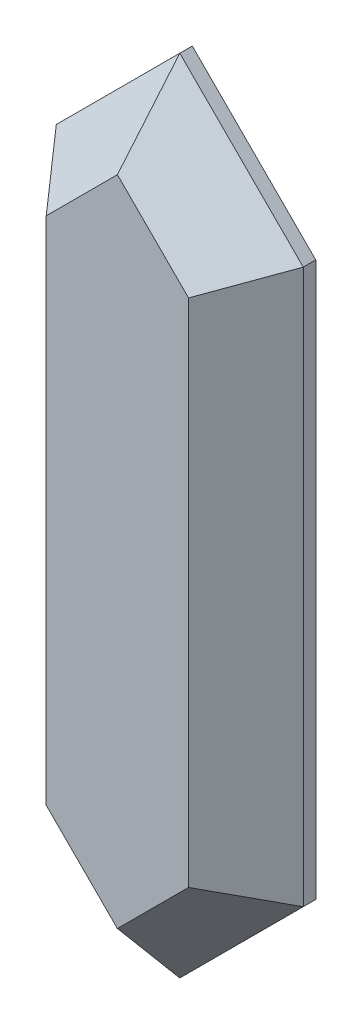
SolidWorks part; units mm, degrees
ref_plane "Спереди" through (0, 0, 0) normal (0, 0, 1) x (1, 0, 0)
ref_plane "Сверху" through (0, 0, 0) normal (0, 1, 0) x (1, 0, 0)
ref_plane "Справа" through (0, 0, 0) normal (1, 0, 0) x (0, 0, -1)
sketch "Skizze1" plane through (0, 0, 0) normal (0, 0, 1) x (1, 0, 0)
  line L0 (-19.799, 44.3) -> (0, 64.099)
  line L1 (0, 64.099) -> (19.799, 44.3)
  line L2 (19.799, 44.3) -> (19.799, -44.5)
  line L3 (19.799, -44.5) -> (0, -64.299)
  line L4 (0, -64.299) -> (-19.799, -44.5)
  line L5 (-19.799, -44.5) -> (-19.799, 44.3)
  line L6 (0, -64.299) -> (0, 76.8777) construction
  line L7 (-19.799, -44.5) -> (59.397, -44.5) construction
  dimension "D1" = 90
  dimension "D2" = 88.8
  dimension "D3" = 28
  dimension "D4" = 90
  dimension "D5" = 44.5
extrude "Бобышка-Вытянуть1" add sketch "Skizze1" along normal blind 2
sketch "Эскиз1" plane through (0, 0, 2) normal (0, 0, 1) x (1, 0, 0)
  line L6 (-19.799, 44.3) -> (-19.799, -44.5)
  line L7 (-19.799, -44.5) -> (0, -64.299)
  line L8 (0, -64.299) -> (19.799, -44.5)
  line L9 (19.799, -44.5) -> (19.799, 44.3)
  line L10 (19.799, 44.3) -> (0, 64.099)
  line L11 (0, 64.099) -> (-19.799, 44.3)
  line L12 (-19.799, 44.3) -> (-19.799, -44.5)
  line L13 (-19.799, -44.5) -> (0, -64.299)
  line L14 (0, -64.299) -> (19.799, -44.5)
  line L15 (19.799, -44.5) -> (19.799, 44.3)
  line L16 (19.799, 44.3) -> (0, 64.099)
  line L17 (0, 64.099) -> (-19.799, 44.3)
  dimension "D1" = 0
extrude "Бобышка-Вытянуть2" add sketch "Эскиз1" along normal blind 10 draft 40
sketch "Эскиз2" plane through (0, 0, 0) normal (0, 0, -1) x (-1, 0, 0)
  line L0 (-17.999, 43.5544) -> (0, 61.5534)
  line L1 (0, 61.5534) -> (17.999, 43.5544)
  line L2 (17.999, 43.5544) -> (17.999, -43.7544)
  line L3 (17.999, -43.7544) -> (0, -61.7534)
  line L4 (0, -61.7534) -> (-17.999, -43.7544)
  line L5 (-17.999, -43.7544) -> (-17.999, 43.5544)
  line L6 (-19.799, 44.3) -> (0, 64.099) construction
  line L7 (0, 64.099) -> (19.799, 44.3) construction
  line L8 (-19.799, -44.5) -> (-19.799, 44.3) construction
  line L9 (0, -64.299) -> (-19.799, -44.5) construction
  line L10 (19.799, -44.5) -> (0, -64.299) construction
  line L11 (19.799, 44.3) -> (19.799, -44.5) construction
  dimension "D1" = 1.8
  dimension "D2" = 1.8
  dimension "D3" = 1.8
  dimension "D4" = 1.8
  dimension "D5" = 1.8
  dimension "D6" = 1.8
extrude "Вырез-Вытянуть1" cut sketch "Эскиз2" against normal blind 2
sketch "Эскиз3" plane through (0, 0, 2) normal (0, 0, -1) x (-1, 0, 0)
  line L6 (-17.999, 43.5544) -> (-17.999, -43.7544)
  line L7 (-17.999, -43.7544) -> (0, -61.7534)
  line L8 (0, -61.7534) -> (17.999, -43.7544)
  line L9 (17.999, -43.7544) -> (17.999, 43.5544)
  line L10 (17.999, 43.5544) -> (0, 61.5534)
  line L11 (0, 61.5534) -> (-17.999, 43.5544)
  line L12 (-17.999, 43.5544) -> (-17.999, -43.7544)
  line L13 (-17.999, -43.7544) -> (0, -61.7534)
  line L14 (0, -61.7534) -> (17.999, -43.7544)
  line L15 (17.999, -43.7544) -> (17.999, 43.5544)
  line L16 (17.999, 43.5544) -> (0, 61.5534)
  line L17 (0, 61.5534) -> (-17.999, 43.5544)
  dimension "D1" = 0
extrude "Вырез-Вытянуть2" cut sketch "Эскиз3" against normal blind 7 draft 40
sketch "Эскиз4" plane through (0, 0, 9) normal (0, 0, -1) x (-1, 0, 0)
  line L12 (-0.6625, 48.8702) -> (-1.7495, 49.4689)
  line L13 (-1.7495, 49.4689) -> (-2.8115, 48.827)
  line L14 (-2.8115, 48.827) -> (-2.7865, 47.5863)
  line L15 (-2.7865, 47.5863) -> (-1.6996, 46.9876)
  line L16 (-1.6996, 46.9876) -> (-0.6376, 47.6295)
  line L17 (-0.6376, 47.6295) -> (-0.6625, 48.8702)
  line L18 (2.7875, 48.8702) -> (1.7005, 49.4689)
  line L19 (1.7005, 49.4689) -> (0.6385, 48.827)
  line L20 (0.6385, 48.827) -> (0.6635, 47.5863)
  line L21 (0.6635, 47.5863) -> (1.7504, 46.9876)
  line L22 (1.7504, 46.9876) -> (2.8124, 47.6295)
  line L23 (2.8124, 47.6295) -> (2.7875, 48.8702)
  line L36 (-4.1125, 44.8702) -> (-5.1995, 45.4689)
  line L37 (-5.1995, 45.4689) -> (-6.2615, 44.827)
  line L38 (-6.2615, 44.827) -> (-6.2365, 43.5863)
  line L39 (-6.2365, 43.5863) -> (-5.1496, 42.9876)
  line L40 (-5.1496, 42.9876) -> (-4.0876, 43.6295)
  line L41 (-4.0876, 43.6295) -> (-4.1125, 44.8702)
  line L42 (-0.6625, 44.8702) -> (-1.7495, 45.4689)
  line L43 (-1.7495, 45.4689) -> (-2.8115, 44.827)
  line L44 (-2.8115, 44.827) -> (-2.7865, 43.5863)
  line L45 (-2.7865, 43.5863) -> (-1.6996, 42.9876)
  line L46 (-1.6996, 42.9876) -> (-0.6376, 43.6295)
  line L47 (-0.6376, 43.6295) -> (-0.6625, 44.8702)
  line L48 (2.7875, 44.8702) -> (1.7005, 45.4689)
  line L49 (1.7005, 45.4689) -> (0.6385, 44.827)
  line L50 (0.6385, 44.827) -> (0.6635, 43.5863)
  line L51 (0.6635, 43.5863) -> (1.7504, 42.9876)
  line L52 (1.7504, 42.9876) -> (2.8124, 43.6295)
  line L53 (2.8124, 43.6295) -> (2.7875, 44.8702)
  line L54 (6.2375, 44.8702) -> (5.1505, 45.4689)
  line L55 (5.1505, 45.4689) -> (4.0885, 44.827)
  line L56 (4.0885, 44.827) -> (4.1135, 43.5863)
  line L57 (4.1135, 43.5863) -> (5.2004, 42.9876)
  line L58 (5.2004, 42.9876) -> (6.2624, 43.6295)
  line L59 (6.2624, 43.6295) -> (6.2375, 44.8702)
  line L66 (-4.1125, 40.8702) -> (-5.1995, 41.4689)
  line L67 (-5.1995, 41.4689) -> (-6.2615, 40.827)
  line L68 (-6.2615, 40.827) -> (-6.2365, 39.5863)
  line L69 (-6.2365, 39.5863) -> (-5.1496, 38.9876)
  line L70 (-5.1496, 38.9876) -> (-4.0876, 39.6295)
  line L71 (-4.0876, 39.6295) -> (-4.1125, 40.8702)
  line L72 (-0.6625, 40.8702) -> (-1.7495, 41.4689)
  line L73 (-1.7495, 41.4689) -> (-2.8115, 40.827)
  line L74 (-2.8115, 40.827) -> (-2.7865, 39.5863)
  line L75 (-2.7865, 39.5863) -> (-1.6996, 38.9876)
  line L76 (-1.6996, 38.9876) -> (-0.6376, 39.6295)
  line L77 (-0.6376, 39.6295) -> (-0.6625, 40.8702)
  line L78 (2.7875, 40.8702) -> (1.7005, 41.4689)
  line L79 (1.7005, 41.4689) -> (0.6385, 40.827)
  line L80 (0.6385, 40.827) -> (0.6635, 39.5863)
  line L81 (0.6635, 39.5863) -> (1.7504, 38.9876)
  line L82 (1.7504, 38.9876) -> (2.8124, 39.6295)
  line L83 (2.8124, 39.6295) -> (2.7875, 40.8702)
  line L84 (6.2375, 40.8702) -> (5.1505, 41.4689)
  line L85 (5.1505, 41.4689) -> (4.0885, 40.827)
  line L86 (4.0885, 40.827) -> (4.1135, 39.5863)
  line L87 (4.1135, 39.5863) -> (5.2004, 38.9876)
  line L88 (5.2004, 38.9876) -> (6.2624, 39.6295)
  line L89 (6.2624, 39.6295) -> (6.2375, 40.8702)
  line L90 (9.6875, 40.8702) -> (8.6005, 41.4689)
  line L91 (8.6005, 41.4689) -> (7.5385, 40.827)
  line L92 (7.5385, 40.827) -> (7.5635, 39.5863)
  line L93 (7.5635, 39.5863) -> (8.6504, 38.9876)
  line L94 (8.6504, 38.9876) -> (9.7124, 39.6295)
  line L95 (9.7124, 39.6295) -> (9.6875, 40.8702)
  line L96 (-4.1125, 36.8702) -> (-5.1995, 37.4689)
  line L97 (-5.1995, 37.4689) -> (-6.2615, 36.827)
  line L98 (-6.2615, 36.827) -> (-6.2365, 35.5863)
  line L99 (-6.2365, 35.5863) -> (-5.1496, 34.9876)
  line L100 (-5.1496, 34.9876) -> (-4.0876, 35.6295)
  line L101 (-4.0876, 35.6295) -> (-4.1125, 36.8702)
  line L102 (-0.6625, 36.8702) -> (-1.7495, 37.4689)
  line L103 (-1.7495, 37.4689) -> (-2.8115, 36.827)
  line L104 (-2.8115, 36.827) -> (-2.7865, 35.5863)
  line L105 (-2.7865, 35.5863) -> (-1.6996, 34.9876)
  line L106 (-1.6996, 34.9876) -> (-0.6376, 35.6295)
  line L107 (-0.6376, 35.6295) -> (-0.6625, 36.8702)
  line L108 (2.7875, 36.8702) -> (1.7005, 37.4689)
  line L109 (1.7005, 37.4689) -> (0.6385, 36.827)
  line L110 (0.6385, 36.827) -> (0.6635, 35.5863)
  line L111 (0.6635, 35.5863) -> (1.7504, 34.9876)
  line L112 (1.7504, 34.9876) -> (2.8124, 35.6295)
  line L113 (2.8124, 35.6295) -> (2.7875, 36.8702)
  line L114 (6.2375, 36.8702) -> (5.1505, 37.4689)
  line L115 (5.1505, 37.4689) -> (4.0885, 36.827)
  line L116 (4.0885, 36.827) -> (4.1135, 35.5863)
  line L117 (4.1135, 35.5863) -> (5.2004, 34.9876)
  line L118 (5.2004, 34.9876) -> (6.2624, 35.6295)
  line L119 (6.2624, 35.6295) -> (6.2375, 36.8702)
  line L120 (9.6875, 36.8702) -> (8.6005, 37.4689)
  line L121 (8.6005, 37.4689) -> (7.5385, 36.827)
  line L122 (7.5385, 36.827) -> (7.5635, 35.5863)
  line L123 (7.5635, 35.5863) -> (8.6504, 34.9876)
  line L124 (8.6504, 34.9876) -> (9.7124, 35.6295)
  line L125 (9.7124, 35.6295) -> (9.6875, 36.8702)
  line L126 (-4.1125, 32.8702) -> (-5.1995, 33.4689)
  line L127 (-5.1995, 33.4689) -> (-6.2615, 32.827)
  line L128 (-6.2615, 32.827) -> (-6.2365, 31.5863)
  line L129 (-6.2365, 31.5863) -> (-5.1496, 30.9876)
  line L130 (-5.1496, 30.9876) -> (-4.0876, 31.6295)
  line L131 (-4.0876, 31.6295) -> (-4.1125, 32.8702)
  line L132 (-0.6625, 32.8702) -> (-1.7495, 33.4689)
  line L133 (-1.7495, 33.4689) -> (-2.8115, 32.827)
  line L134 (-2.8115, 32.827) -> (-2.7865, 31.5863)
  line L135 (-2.7865, 31.5863) -> (-1.6996, 30.9876)
  line L136 (-1.6996, 30.9876) -> (-0.6376, 31.6295)
  line L137 (-0.6376, 31.6295) -> (-0.6625, 32.8702)
  line L138 (2.7875, 32.8702) -> (1.7005, 33.4689)
  line L139 (1.7005, 33.4689) -> (0.6385, 32.827)
  line L140 (0.6385, 32.827) -> (0.6635, 31.5863)
  line L141 (0.6635, 31.5863) -> (1.7504, 30.9876)
  line L142 (1.7504, 30.9876) -> (2.8124, 31.6295)
  line L143 (2.8124, 31.6295) -> (2.7875, 32.8702)
  line L144 (6.2375, 32.8702) -> (5.1505, 33.4689)
  line L145 (5.1505, 33.4689) -> (4.0885, 32.827)
  line L146 (4.0885, 32.827) -> (4.1135, 31.5863)
  line L147 (4.1135, 31.5863) -> (5.2004, 30.9876)
  line L148 (5.2004, 30.9876) -> (6.2624, 31.6295)
  line L149 (6.2624, 31.6295) -> (6.2375, 32.8702)
  line L150 (9.6875, 32.8702) -> (8.6005, 33.4689)
  line L151 (8.6005, 33.4689) -> (7.5385, 32.827)
  line L152 (7.5385, 32.827) -> (7.5635, 31.5863)
  line L153 (7.5635, 31.5863) -> (8.6504, 30.9876)
  line L154 (8.6504, 30.9876) -> (9.7124, 31.6295)
  line L155 (9.7124, 31.6295) -> (9.6875, 32.8702)
  line L156 (-4.1125, 28.8702) -> (-5.1995, 29.4689)
  line L157 (-5.1995, 29.4689) -> (-6.2615, 28.827)
  line L158 (-6.2615, 28.827) -> (-6.2365, 27.5863)
  line L159 (-6.2365, 27.5863) -> (-5.1496, 26.9876)
  line L160 (-5.1496, 26.9876) -> (-4.0876, 27.6295)
  line L161 (-4.0876, 27.6295) -> (-4.1125, 28.8702)
  line L162 (-0.6625, 28.8702) -> (-1.7495, 29.4689)
  line L163 (-1.7495, 29.4689) -> (-2.8115, 28.827)
  line L164 (-2.8115, 28.827) -> (-2.7865, 27.5863)
  line L165 (-2.7865, 27.5863) -> (-1.6996, 26.9876)
  line L166 (-1.6996, 26.9876) -> (-0.6376, 27.6295)
  line L167 (-0.6376, 27.6295) -> (-0.6625, 28.8702)
  line L168 (2.7875, 28.8702) -> (1.7005, 29.4689)
  line L169 (1.7005, 29.4689) -> (0.6385, 28.827)
  line L170 (0.6385, 28.827) -> (0.6635, 27.5863)
  line L171 (0.6635, 27.5863) -> (1.7504, 26.9876)
  line L172 (1.7504, 26.9876) -> (2.8124, 27.6295)
  line L173 (2.8124, 27.6295) -> (2.7875, 28.8702)
  line L174 (6.2375, 28.8702) -> (5.1505, 29.4689)
  line L175 (5.1505, 29.4689) -> (4.0885, 28.827)
  line L176 (4.0885, 28.827) -> (4.1135, 27.5863)
  line L177 (4.1135, 27.5863) -> (5.2004, 26.9876)
  line L178 (5.2004, 26.9876) -> (6.2624, 27.6295)
  line L179 (6.2624, 27.6295) -> (6.2375, 28.8702)
  line L180 (9.6875, 28.8702) -> (8.6005, 29.4689)
  line L181 (8.6005, 29.4689) -> (7.5385, 28.827)
  line L182 (7.5385, 28.827) -> (7.5635, 27.5863)
  line L183 (7.5635, 27.5863) -> (8.6504, 26.9876)
  line L184 (8.6504, 26.9876) -> (9.7124, 27.6295)
  line L185 (9.7124, 27.6295) -> (9.6875, 28.8702)
  line L186 (-4.1125, 24.8702) -> (-5.1995, 25.4689)
  line L187 (-5.1995, 25.4689) -> (-6.2615, 24.827)
  line L188 (-6.2615, 24.827) -> (-6.2365, 23.5863)
  line L189 (-6.2365, 23.5863) -> (-5.1496, 22.9876)
  line L190 (-5.1496, 22.9876) -> (-4.0876, 23.6295)
  line L191 (-4.0876, 23.6295) -> (-4.1125, 24.8702)
  line L192 (-0.6625, 24.8702) -> (-1.7495, 25.4689)
  line L193 (-1.7495, 25.4689) -> (-2.8115, 24.827)
  line L194 (-2.8115, 24.827) -> (-2.7865, 23.5863)
  line L195 (-2.7865, 23.5863) -> (-1.6996, 22.9876)
  line L196 (-1.6996, 22.9876) -> (-0.6376, 23.6295)
  line L197 (-0.6376, 23.6295) -> (-0.6625, 24.8702)
  line L198 (2.7875, 24.8702) -> (1.7005, 25.4689)
  line L199 (1.7005, 25.4689) -> (0.6385, 24.827)
  line L200 (0.6385, 24.827) -> (0.6635, 23.5863)
  line L201 (0.6635, 23.5863) -> (1.7504, 22.9876)
  line L202 (1.7504, 22.9876) -> (2.8124, 23.6295)
  line L203 (2.8124, 23.6295) -> (2.7875, 24.8702)
  line L204 (6.2375, 24.8702) -> (5.1505, 25.4689)
  line L205 (5.1505, 25.4689) -> (4.0885, 24.827)
  line L206 (4.0885, 24.827) -> (4.1135, 23.5863)
  line L207 (4.1135, 23.5863) -> (5.2004, 22.9876)
  line L208 (5.2004, 22.9876) -> (6.2624, 23.6295)
  line L209 (6.2624, 23.6295) -> (6.2375, 24.8702)
  line L210 (9.6875, 24.8702) -> (8.6005, 25.4689)
  line L211 (8.6005, 25.4689) -> (7.5385, 24.827)
  line L212 (7.5385, 24.827) -> (7.5635, 23.5863)
  line L213 (7.5635, 23.5863) -> (8.6504, 22.9876)
  line L214 (8.6504, 22.9876) -> (9.7124, 23.6295)
  line L215 (9.7124, 23.6295) -> (9.6875, 24.8702)
  line L216 (-4.1125, 20.8702) -> (-5.1995, 21.4689)
  line L217 (-5.1995, 21.4689) -> (-6.2615, 20.827)
  line L218 (-6.2615, 20.827) -> (-6.2365, 19.5863)
  line L219 (-6.2365, 19.5863) -> (-5.1496, 18.9876)
  line L220 (-5.1496, 18.9876) -> (-4.0876, 19.6295)
  line L221 (-4.0876, 19.6295) -> (-4.1125, 20.8702)
  line L222 (-0.6625, 20.8702) -> (-1.7495, 21.4689)
  line L223 (-1.7495, 21.4689) -> (-2.8115, 20.827)
  line L224 (-2.8115, 20.827) -> (-2.7865, 19.5863)
  line L225 (-2.7865, 19.5863) -> (-1.6996, 18.9876)
  line L226 (-1.6996, 18.9876) -> (-0.6376, 19.6295)
  line L227 (-0.6376, 19.6295) -> (-0.6625, 20.8702)
  line L228 (2.7875, 20.8702) -> (1.7005, 21.4689)
  line L229 (1.7005, 21.4689) -> (0.6385, 20.827)
  line L230 (0.6385, 20.827) -> (0.6635, 19.5863)
  line L231 (0.6635, 19.5863) -> (1.7504, 18.9876)
  line L232 (1.7504, 18.9876) -> (2.8124, 19.6295)
  line L233 (2.8124, 19.6295) -> (2.7875, 20.8702)
  line L234 (6.2375, 20.8702) -> (5.1505, 21.4689)
  line L235 (5.1505, 21.4689) -> (4.0885, 20.827)
  line L236 (4.0885, 20.827) -> (4.1135, 19.5863)
  line L237 (4.1135, 19.5863) -> (5.2004, 18.9876)
  line L238 (5.2004, 18.9876) -> (6.2624, 19.6295)
  line L239 (6.2624, 19.6295) -> (6.2375, 20.8702)
  line L240 (9.6875, 20.8702) -> (8.6005, 21.4689)
  line L241 (8.6005, 21.4689) -> (7.5385, 20.827)
  line L242 (7.5385, 20.827) -> (7.5635, 19.5863)
  line L243 (7.5635, 19.5863) -> (8.6504, 18.9876)
  line L244 (8.6504, 18.9876) -> (9.7124, 19.6295)
  line L245 (9.7124, 19.6295) -> (9.6875, 20.8702)
  line L246 (-4.1125, 16.8702) -> (-5.1995, 17.4689)
  line L247 (-5.1995, 17.4689) -> (-6.2615, 16.827)
  line L248 (-6.2615, 16.827) -> (-6.2365, 15.5863)
  line L249 (-6.2365, 15.5863) -> (-5.1496, 14.9876)
  line L250 (-5.1496, 14.9876) -> (-4.0876, 15.6295)
  line L251 (-4.0876, 15.6295) -> (-4.1125, 16.8702)
  line L252 (-0.6625, 16.8702) -> (-1.7495, 17.4689)
  line L253 (-1.7495, 17.4689) -> (-2.8115, 16.827)
  line L254 (-2.8115, 16.827) -> (-2.7865, 15.5863)
  line L255 (-2.7865, 15.5863) -> (-1.6996, 14.9876)
  line L256 (-1.6996, 14.9876) -> (-0.6376, 15.6295)
  line L257 (-0.6376, 15.6295) -> (-0.6625, 16.8702)
  line L258 (2.7875, 16.8702) -> (1.7005, 17.4689)
  line L259 (1.7005, 17.4689) -> (0.6385, 16.827)
  line L260 (0.6385, 16.827) -> (0.6635, 15.5863)
  line L261 (0.6635, 15.5863) -> (1.7504, 14.9876)
  line L262 (1.7504, 14.9876) -> (2.8124, 15.6295)
  line L263 (2.8124, 15.6295) -> (2.7875, 16.8702)
  line L264 (6.2375, 16.8702) -> (5.1505, 17.4689)
  line L265 (5.1505, 17.4689) -> (4.0885, 16.827)
  line L266 (4.0885, 16.827) -> (4.1135, 15.5863)
  line L267 (4.1135, 15.5863) -> (5.2004, 14.9876)
  line L268 (5.2004, 14.9876) -> (6.2624, 15.6295)
  line L269 (6.2624, 15.6295) -> (6.2375, 16.8702)
  line L270 (9.6875, 16.8702) -> (8.6005, 17.4689)
  line L271 (8.6005, 17.4689) -> (7.5385, 16.827)
  line L272 (7.5385, 16.827) -> (7.5635, 15.5863)
  line L273 (7.5635, 15.5863) -> (8.6504, 14.9876)
  line L274 (8.6504, 14.9876) -> (9.7124, 15.6295)
  line L275 (9.7124, 15.6295) -> (9.6875, 16.8702)
  line L276 (-4.1125, 12.8702) -> (-5.1995, 13.4689)
  line L277 (-5.1995, 13.4689) -> (-6.2615, 12.827)
  line L278 (-6.2615, 12.827) -> (-6.2365, 11.5863)
  line L279 (-6.2365, 11.5863) -> (-5.1496, 10.9876)
  line L280 (-5.1496, 10.9876) -> (-4.0876, 11.6295)
  line L281 (-4.0876, 11.6295) -> (-4.1125, 12.8702)
  line L282 (-0.6625, 12.8702) -> (-1.7495, 13.4689)
  line L283 (-1.7495, 13.4689) -> (-2.8115, 12.827)
  line L284 (-2.8115, 12.827) -> (-2.7865, 11.5863)
  line L285 (-2.7865, 11.5863) -> (-1.6996, 10.9876)
  line L286 (-1.6996, 10.9876) -> (-0.6376, 11.6295)
  line L287 (-0.6376, 11.6295) -> (-0.6625, 12.8702)
  line L288 (2.7875, 12.8702) -> (1.7005, 13.4689)
  line L289 (1.7005, 13.4689) -> (0.6385, 12.827)
  line L290 (0.6385, 12.827) -> (0.6635, 11.5863)
  line L291 (0.6635, 11.5863) -> (1.7504, 10.9876)
  line L292 (1.7504, 10.9876) -> (2.8124, 11.6295)
  line L293 (2.8124, 11.6295) -> (2.7875, 12.8702)
  line L294 (6.2375, 12.8702) -> (5.1505, 13.4689)
  line L295 (5.1505, 13.4689) -> (4.0885, 12.827)
  line L296 (4.0885, 12.827) -> (4.1135, 11.5863)
  line L297 (4.1135, 11.5863) -> (5.2004, 10.9876)
  line L298 (5.2004, 10.9876) -> (6.2624, 11.6295)
  line L299 (6.2624, 11.6295) -> (6.2375, 12.8702)
  line L300 (9.6875, 12.8702) -> (8.6005, 13.4689)
  line L301 (8.6005, 13.4689) -> (7.5385, 12.827)
  line L302 (7.5385, 12.827) -> (7.5635, 11.5863)
  line L303 (7.5635, 11.5863) -> (8.6504, 10.9876)
  line L304 (8.6504, 10.9876) -> (9.7124, 11.6295)
  line L305 (9.7124, 11.6295) -> (9.6875, 12.8702)
  line L306 (-4.1125, 8.8702) -> (-5.1995, 9.4689)
  line L307 (-5.1995, 9.4689) -> (-6.2615, 8.827)
  line L308 (-6.2615, 8.827) -> (-6.2365, 7.5863)
  line L309 (-6.2365, 7.5863) -> (-5.1496, 6.9876)
  line L310 (-5.1496, 6.9876) -> (-4.0876, 7.6295)
  line L311 (-4.0876, 7.6295) -> (-4.1125, 8.8702)
  line L312 (-0.6625, 8.8702) -> (-1.7495, 9.4689)
  line L313 (-1.7495, 9.4689) -> (-2.8115, 8.827)
  line L314 (-2.8115, 8.827) -> (-2.7865, 7.5863)
  line L315 (-2.7865, 7.5863) -> (-1.6996, 6.9876)
  line L316 (-1.6996, 6.9876) -> (-0.6376, 7.6295)
  line L317 (-0.6376, 7.6295) -> (-0.6625, 8.8702)
  line L318 (2.7875, 8.8702) -> (1.7005, 9.4689)
  line L319 (1.7005, 9.4689) -> (0.6385, 8.827)
  line L320 (0.6385, 8.827) -> (0.6635, 7.5863)
  line L321 (0.6635, 7.5863) -> (1.7504, 6.9876)
  line L322 (1.7504, 6.9876) -> (2.8124, 7.6295)
  line L323 (2.8124, 7.6295) -> (2.7875, 8.8702)
  line L324 (6.2375, 8.8702) -> (5.1505, 9.4689)
  line L325 (5.1505, 9.4689) -> (4.0885, 8.827)
  line L326 (4.0885, 8.827) -> (4.1135, 7.5863)
  line L327 (4.1135, 7.5863) -> (5.2004, 6.9876)
  line L328 (5.2004, 6.9876) -> (6.2624, 7.6295)
  line L329 (6.2624, 7.6295) -> (6.2375, 8.8702)
  line L330 (9.6875, 8.8702) -> (8.6005, 9.4689)
  line L331 (8.6005, 9.4689) -> (7.5385, 8.827)
  line L332 (7.5385, 8.827) -> (7.5635, 7.5863)
  line L333 (7.5635, 7.5863) -> (8.6504, 6.9876)
  line L334 (8.6504, 6.9876) -> (9.7124, 7.6295)
  line L335 (9.7124, 7.6295) -> (9.6875, 8.8702)
  line L336 (-4.1125, 4.8702) -> (-5.1995, 5.4689)
  line L337 (-5.1995, 5.4689) -> (-6.2615, 4.827)
  line L338 (-6.2615, 4.827) -> (-6.2365, 3.5863)
  line L339 (-6.2365, 3.5863) -> (-5.1496, 2.9876)
  line L340 (-5.1496, 2.9876) -> (-4.0876, 3.6295)
  line L341 (-4.0876, 3.6295) -> (-4.1125, 4.8702)
  line L342 (-0.6625, 4.8702) -> (-1.7495, 5.4689)
  line L343 (-1.7495, 5.4689) -> (-2.8115, 4.827)
  line L344 (-2.8115, 4.827) -> (-2.7865, 3.5863)
  line L345 (-2.7865, 3.5863) -> (-1.6996, 2.9876)
  line L346 (-1.6996, 2.9876) -> (-0.6376, 3.6295)
  line L347 (-0.6376, 3.6295) -> (-0.6625, 4.8702)
  line L348 (2.7875, 4.8702) -> (1.7005, 5.4689)
  line L349 (1.7005, 5.4689) -> (0.6385, 4.827)
  line L350 (0.6385, 4.827) -> (0.6635, 3.5863)
  line L351 (0.6635, 3.5863) -> (1.7504, 2.9876)
  line L352 (1.7504, 2.9876) -> (2.8124, 3.6295)
  line L353 (2.8124, 3.6295) -> (2.7875, 4.8702)
  line L354 (6.2375, 4.8702) -> (5.1505, 5.4689)
  line L355 (5.1505, 5.4689) -> (4.0885, 4.827)
  line L356 (4.0885, 4.827) -> (4.1135, 3.5863)
  line L357 (4.1135, 3.5863) -> (5.2004, 2.9876)
  line L358 (5.2004, 2.9876) -> (6.2624, 3.6295)
  line L359 (6.2624, 3.6295) -> (6.2375, 4.8702)
  line L360 (9.6875, 4.8702) -> (8.6005, 5.4689)
  line L361 (8.6005, 5.4689) -> (7.5385, 4.827)
  line L362 (7.5385, 4.827) -> (7.5635, 3.5863)
  line L363 (7.5635, 3.5863) -> (8.6504, 2.9876)
  line L364 (8.6504, 2.9876) -> (9.7124, 3.6295)
  line L365 (9.7124, 3.6295) -> (9.6875, 4.8702)
  line L366 (-4.1125, 0.8702) -> (-5.1995, 1.4689)
  line L367 (-5.1995, 1.4689) -> (-6.2615, 0.827)
  line L368 (-6.2615, 0.827) -> (-6.2365, -0.4137)
  line L369 (-6.2365, -0.4137) -> (-5.1496, -1.0124)
  line L370 (-5.1496, -1.0124) -> (-4.0876, -0.3705)
  line L371 (-4.0876, -0.3705) -> (-4.1125, 0.8702)
  line L372 (-0.6625, 0.8702) -> (-1.7495, 1.4689)
  line L373 (-1.7495, 1.4689) -> (-2.8115, 0.827)
  line L374 (-2.8115, 0.827) -> (-2.7865, -0.4137)
  line L375 (-2.7865, -0.4137) -> (-1.6996, -1.0124)
  line L376 (-1.6996, -1.0124) -> (-0.6376, -0.3705)
  line L377 (-0.6376, -0.3705) -> (-0.6625, 0.8702)
  line L378 (2.7875, 0.8702) -> (1.7005, 1.4689)
  line L379 (1.7005, 1.4689) -> (0.6385, 0.827)
  line L380 (0.6385, 0.827) -> (0.6635, -0.4137)
  line L381 (0.6635, -0.4137) -> (1.7504, -1.0124)
  line L382 (1.7504, -1.0124) -> (2.8124, -0.3705)
  line L383 (2.8124, -0.3705) -> (2.7875, 0.8702)
  line L384 (6.2375, 0.8702) -> (5.1505, 1.4689)
  line L385 (5.1505, 1.4689) -> (4.0885, 0.827)
  line L386 (4.0885, 0.827) -> (4.1135, -0.4137)
  line L387 (4.1135, -0.4137) -> (5.2004, -1.0124)
  line L388 (5.2004, -1.0124) -> (6.2624, -0.3705)
  line L389 (6.2624, -0.3705) -> (6.2375, 0.8702)
  line L390 (9.6875, 0.8702) -> (8.6005, 1.4689)
  line L391 (8.6005, 1.4689) -> (7.5385, 0.827)
  line L392 (7.5385, 0.827) -> (7.5635, -0.4137)
  line L393 (7.5635, -0.4137) -> (8.6504, -1.0124)
  line L394 (8.6504, -1.0124) -> (9.7124, -0.3705)
  line L395 (9.7124, -0.3705) -> (9.6875, 0.8702)
  line L396 (-4.1125, -3.1298) -> (-5.1995, -2.5311)
  line L397 (-5.1995, -2.5311) -> (-6.2615, -3.173)
  line L398 (-6.2615, -3.173) -> (-6.2365, -4.4137)
  line L399 (-6.2365, -4.4137) -> (-5.1496, -5.0124)
  line L400 (-5.1496, -5.0124) -> (-4.0876, -4.3705)
  line L401 (-4.0876, -4.3705) -> (-4.1125, -3.1298)
  line L402 (-0.6625, -3.1298) -> (-1.7495, -2.5311)
  line L403 (-1.7495, -2.5311) -> (-2.8115, -3.173)
  line L404 (-2.8115, -3.173) -> (-2.7865, -4.4137)
  line L405 (-2.7865, -4.4137) -> (-1.6996, -5.0124)
  line L406 (-1.6996, -5.0124) -> (-0.6376, -4.3705)
  line L407 (-0.6376, -4.3705) -> (-0.6625, -3.1298)
  line L408 (2.7875, -3.1298) -> (1.7005, -2.5311)
  line L409 (1.7005, -2.5311) -> (0.6385, -3.173)
  line L410 (0.6385, -3.173) -> (0.6635, -4.4137)
  line L411 (0.6635, -4.4137) -> (1.7504, -5.0124)
  line L412 (1.7504, -5.0124) -> (2.8124, -4.3705)
  line L413 (2.8124, -4.3705) -> (2.7875, -3.1298)
  line L414 (6.2375, -3.1298) -> (5.1505, -2.5311)
  line L415 (5.1505, -2.5311) -> (4.0885, -3.173)
  line L416 (4.0885, -3.173) -> (4.1135, -4.4137)
  line L417 (4.1135, -4.4137) -> (5.2004, -5.0124)
  line L418 (5.2004, -5.0124) -> (6.2624, -4.3705)
  line L419 (6.2624, -4.3705) -> (6.2375, -3.1298)
  line L420 (9.6875, -3.1298) -> (8.6005, -2.5311)
  line L421 (8.6005, -2.5311) -> (7.5385, -3.173)
  line L422 (7.5385, -3.173) -> (7.5635, -4.4137)
  line L423 (7.5635, -4.4137) -> (8.6504, -5.0124)
  line L424 (8.6504, -5.0124) -> (9.7124, -4.3705)
  line L425 (9.7124, -4.3705) -> (9.6875, -3.1298)
  line L426 (-4.1125, -7.1298) -> (-5.1995, -6.5311)
  line L427 (-5.1995, -6.5311) -> (-6.2615, -7.173)
  line L428 (-6.2615, -7.173) -> (-6.2365, -8.4137)
  line L429 (-6.2365, -8.4137) -> (-5.1496, -9.0124)
  line L430 (-5.1496, -9.0124) -> (-4.0876, -8.3705)
  line L431 (-4.0876, -8.3705) -> (-4.1125, -7.1298)
  line L432 (-0.6625, -7.1298) -> (-1.7495, -6.5311)
  line L433 (-1.7495, -6.5311) -> (-2.8115, -7.173)
  line L434 (-2.8115, -7.173) -> (-2.7865, -8.4137)
  line L435 (-2.7865, -8.4137) -> (-1.6996, -9.0124)
  line L436 (-1.6996, -9.0124) -> (-0.6376, -8.3705)
  line L437 (-0.6376, -8.3705) -> (-0.6625, -7.1298)
  line L438 (2.7875, -7.1298) -> (1.7005, -6.5311)
  line L439 (1.7005, -6.5311) -> (0.6385, -7.173)
  line L440 (0.6385, -7.173) -> (0.6635, -8.4137)
  line L441 (0.6635, -8.4137) -> (1.7504, -9.0124)
  line L442 (1.7504, -9.0124) -> (2.8124, -8.3705)
  line L443 (2.8124, -8.3705) -> (2.7875, -7.1298)
  line L444 (6.2375, -7.1298) -> (5.1505, -6.5311)
  line L445 (5.1505, -6.5311) -> (4.0885, -7.173)
  line L446 (4.0885, -7.173) -> (4.1135, -8.4137)
  line L447 (4.1135, -8.4137) -> (5.2004, -9.0124)
  line L448 (5.2004, -9.0124) -> (6.2624, -8.3705)
  line L449 (6.2624, -8.3705) -> (6.2375, -7.1298)
  line L450 (9.6875, -7.1298) -> (8.6005, -6.5311)
  line L451 (8.6005, -6.5311) -> (7.5385, -7.173)
  line L452 (7.5385, -7.173) -> (7.5635, -8.4137)
  line L453 (7.5635, -8.4137) -> (8.6504, -9.0124)
  line L454 (8.6504, -9.0124) -> (9.7124, -8.3705)
  line L455 (9.7124, -8.3705) -> (9.6875, -7.1298)
  line L456 (-4.1125, -11.1298) -> (-5.1995, -10.5311)
  line L457 (-5.1995, -10.5311) -> (-6.2615, -11.173)
  line L458 (-6.2615, -11.173) -> (-6.2365, -12.4137)
  line L459 (-6.2365, -12.4137) -> (-5.1496, -13.0124)
  line L460 (-5.1496, -13.0124) -> (-4.0876, -12.3705)
  line L461 (-4.0876, -12.3705) -> (-4.1125, -11.1298)
  line L462 (-0.6625, -11.1298) -> (-1.7495, -10.5311)
  line L463 (-1.7495, -10.5311) -> (-2.8115, -11.173)
  line L464 (-2.8115, -11.173) -> (-2.7865, -12.4137)
  line L465 (-2.7865, -12.4137) -> (-1.6996, -13.0124)
  line L466 (-1.6996, -13.0124) -> (-0.6376, -12.3705)
  line L467 (-0.6376, -12.3705) -> (-0.6625, -11.1298)
  line L468 (2.7875, -11.1298) -> (1.7005, -10.5311)
  line L469 (1.7005, -10.5311) -> (0.6385, -11.173)
  line L470 (0.6385, -11.173) -> (0.6635, -12.4137)
  line L471 (0.6635, -12.4137) -> (1.7504, -13.0124)
  line L472 (1.7504, -13.0124) -> (2.8124, -12.3705)
  line L473 (2.8124, -12.3705) -> (2.7875, -11.1298)
  line L474 (6.2375, -11.1298) -> (5.1505, -10.5311)
  line L475 (5.1505, -10.5311) -> (4.0885, -11.173)
  line L476 (4.0885, -11.173) -> (4.1135, -12.4137)
  line L477 (4.1135, -12.4137) -> (5.2004, -13.0124)
  line L478 (5.2004, -13.0124) -> (6.2624, -12.3705)
  line L479 (6.2624, -12.3705) -> (6.2375, -11.1298)
  line L480 (9.6875, -11.1298) -> (8.6005, -10.5311)
  line L481 (8.6005, -10.5311) -> (7.5385, -11.173)
  line L482 (7.5385, -11.173) -> (7.5635, -12.4137)
  line L483 (7.5635, -12.4137) -> (8.6504, -13.0124)
  line L484 (8.6504, -13.0124) -> (9.7124, -12.3705)
  line L485 (9.7124, -12.3705) -> (9.6875, -11.1298)
  line L486 (-4.1125, -15.1298) -> (-5.1995, -14.5311)
  line L487 (-5.1995, -14.5311) -> (-6.2615, -15.173)
  line L488 (-6.2615, -15.173) -> (-6.2365, -16.4137)
  line L489 (-6.2365, -16.4137) -> (-5.1496, -17.0124)
  line L490 (-5.1496, -17.0124) -> (-4.0876, -16.3705)
  line L491 (-4.0876, -16.3705) -> (-4.1125, -15.1298)
  line L492 (-0.6625, -15.1298) -> (-1.7495, -14.5311)
  line L493 (-1.7495, -14.5311) -> (-2.8115, -15.173)
  line L494 (-2.8115, -15.173) -> (-2.7865, -16.4137)
  line L495 (-2.7865, -16.4137) -> (-1.6996, -17.0124)
  line L496 (-1.6996, -17.0124) -> (-0.6376, -16.3705)
  line L497 (-0.6376, -16.3705) -> (-0.6625, -15.1298)
  line L498 (2.7875, -15.1298) -> (1.7005, -14.5311)
  line L499 (1.7005, -14.5311) -> (0.6385, -15.173)
  line L500 (0.6385, -15.173) -> (0.6635, -16.4137)
  line L501 (0.6635, -16.4137) -> (1.7504, -17.0124)
  line L502 (1.7504, -17.0124) -> (2.8124, -16.3705)
  line L503 (2.8124, -16.3705) -> (2.7875, -15.1298)
  line L504 (6.2375, -15.1298) -> (5.1505, -14.5311)
  line L505 (5.1505, -14.5311) -> (4.0885, -15.173)
  line L506 (4.0885, -15.173) -> (4.1135, -16.4137)
  line L507 (4.1135, -16.4137) -> (5.2004, -17.0124)
  line L508 (5.2004, -17.0124) -> (6.2624, -16.3705)
  line L509 (6.2624, -16.3705) -> (6.2375, -15.1298)
  line L510 (9.6875, -15.1298) -> (8.6005, -14.5311)
  line L511 (8.6005, -14.5311) -> (7.5385, -15.173)
  line L512 (7.5385, -15.173) -> (7.5635, -16.4137)
  line L513 (7.5635, -16.4137) -> (8.6504, -17.0124)
  line L514 (8.6504, -17.0124) -> (9.7124, -16.3705)
  line L515 (9.7124, -16.3705) -> (9.6875, -15.1298)
  line L516 (-4.1125, -19.1298) -> (-5.1995, -18.5311)
  line L517 (-5.1995, -18.5311) -> (-6.2615, -19.173)
  line L518 (-6.2615, -19.173) -> (-6.2365, -20.4137)
  line L519 (-6.2365, -20.4137) -> (-5.1496, -21.0124)
  line L520 (-5.1496, -21.0124) -> (-4.0876, -20.3705)
  line L521 (-4.0876, -20.3705) -> (-4.1125, -19.1298)
  line L522 (-0.6625, -19.1298) -> (-1.7495, -18.5311)
  line L523 (-1.7495, -18.5311) -> (-2.8115, -19.173)
  line L524 (-2.8115, -19.173) -> (-2.7865, -20.4137)
  line L525 (-2.7865, -20.4137) -> (-1.6996, -21.0124)
  line L526 (-1.6996, -21.0124) -> (-0.6376, -20.3705)
  line L527 (-0.6376, -20.3705) -> (-0.6625, -19.1298)
  line L528 (2.7875, -19.1298) -> (1.7005, -18.5311)
  line L529 (1.7005, -18.5311) -> (0.6385, -19.173)
  line L530 (0.6385, -19.173) -> (0.6635, -20.4137)
  line L531 (0.6635, -20.4137) -> (1.7504, -21.0124)
  line L532 (1.7504, -21.0124) -> (2.8124, -20.3705)
  line L533 (2.8124, -20.3705) -> (2.7875, -19.1298)
  line L534 (6.2375, -19.1298) -> (5.1505, -18.5311)
  line L535 (5.1505, -18.5311) -> (4.0885, -19.173)
  line L536 (4.0885, -19.173) -> (4.1135, -20.4137)
  line L537 (4.1135, -20.4137) -> (5.2004, -21.0124)
  line L538 (5.2004, -21.0124) -> (6.2624, -20.3705)
  line L539 (6.2624, -20.3705) -> (6.2375, -19.1298)
  line L540 (9.6875, -19.1298) -> (8.6005, -18.5311)
  line L541 (8.6005, -18.5311) -> (7.5385, -19.173)
  line L542 (7.5385, -19.173) -> (7.5635, -20.4137)
  line L543 (7.5635, -20.4137) -> (8.6504, -21.0124)
  line L544 (8.6504, -21.0124) -> (9.7124, -20.3705)
  line L545 (9.7124, -20.3705) -> (9.6875, -19.1298)
  line L546 (-4.1125, -23.1298) -> (-5.1995, -22.5311)
  line L547 (-5.1995, -22.5311) -> (-6.2615, -23.173)
  line L548 (-6.2615, -23.173) -> (-6.2365, -24.4137)
  line L549 (-6.2365, -24.4137) -> (-5.1496, -25.0124)
  line L550 (-5.1496, -25.0124) -> (-4.0876, -24.3705)
  line L551 (-4.0876, -24.3705) -> (-4.1125, -23.1298)
  line L552 (-0.6625, -23.1298) -> (-1.7495, -22.5311)
  line L553 (-1.7495, -22.5311) -> (-2.8115, -23.173)
  line L554 (-2.8115, -23.173) -> (-2.7865, -24.4137)
  line L555 (-2.7865, -24.4137) -> (-1.6996, -25.0124)
  line L556 (-1.6996, -25.0124) -> (-0.6376, -24.3705)
  line L557 (-0.6376, -24.3705) -> (-0.6625, -23.1298)
  line L558 (2.7875, -23.1298) -> (1.7005, -22.5311)
  line L559 (1.7005, -22.5311) -> (0.6385, -23.173)
  line L560 (0.6385, -23.173) -> (0.6635, -24.4137)
  line L561 (0.6635, -24.4137) -> (1.7504, -25.0124)
  line L562 (1.7504, -25.0124) -> (2.8124, -24.3705)
  line L563 (2.8124, -24.3705) -> (2.7875, -23.1298)
  line L564 (6.2375, -23.1298) -> (5.1505, -22.5311)
  line L565 (5.1505, -22.5311) -> (4.0885, -23.173)
  line L566 (4.0885, -23.173) -> (4.1135, -24.4137)
  line L567 (4.1135, -24.4137) -> (5.2004, -25.0124)
  line L568 (5.2004, -25.0124) -> (6.2624, -24.3705)
  line L569 (6.2624, -24.3705) -> (6.2375, -23.1298)
  line L570 (9.6875, -23.1298) -> (8.6005, -22.5311)
  line L571 (8.6005, -22.5311) -> (7.5385, -23.173)
  line L572 (7.5385, -23.173) -> (7.5635, -24.4137)
  line L573 (7.5635, -24.4137) -> (8.6504, -25.0124)
  line L574 (8.6504, -25.0124) -> (9.7124, -24.3705)
  line L575 (9.7124, -24.3705) -> (9.6875, -23.1298)
  line L576 (-4.1125, -27.1298) -> (-5.1995, -26.5311)
  line L577 (-5.1995, -26.5311) -> (-6.2615, -27.173)
  line L578 (-6.2615, -27.173) -> (-6.2365, -28.4137)
  line L579 (-6.2365, -28.4137) -> (-5.1496, -29.0124)
  line L580 (-5.1496, -29.0124) -> (-4.0876, -28.3705)
  line L581 (-4.0876, -28.3705) -> (-4.1125, -27.1298)
  line L582 (-0.6625, -27.1298) -> (-1.7495, -26.5311)
  line L583 (-1.7495, -26.5311) -> (-2.8115, -27.173)
  line L584 (-2.8115, -27.173) -> (-2.7865, -28.4137)
  line L585 (-2.7865, -28.4137) -> (-1.6996, -29.0124)
  line L586 (-1.6996, -29.0124) -> (-0.6376, -28.3705)
  line L587 (-0.6376, -28.3705) -> (-0.6625, -27.1298)
  line L588 (2.7875, -27.1298) -> (1.7005, -26.5311)
  line L589 (1.7005, -26.5311) -> (0.6385, -27.173)
  line L590 (0.6385, -27.173) -> (0.6635, -28.4137)
  line L591 (0.6635, -28.4137) -> (1.7504, -29.0124)
  line L592 (1.7504, -29.0124) -> (2.8124, -28.3705)
  line L593 (2.8124, -28.3705) -> (2.7875, -27.1298)
  line L594 (6.2375, -27.1298) -> (5.1505, -26.5311)
  line L595 (5.1505, -26.5311) -> (4.0885, -27.173)
  line L596 (4.0885, -27.173) -> (4.1135, -28.4137)
  line L597 (4.1135, -28.4137) -> (5.2004, -29.0124)
  line L598 (5.2004, -29.0124) -> (6.2624, -28.3705)
  line L599 (6.2624, -28.3705) -> (6.2375, -27.1298)
  line L600 (9.6875, -27.1298) -> (8.6005, -26.5311)
  line L601 (8.6005, -26.5311) -> (7.5385, -27.173)
  line L602 (7.5385, -27.173) -> (7.5635, -28.4137)
  line L603 (7.5635, -28.4137) -> (8.6504, -29.0124)
  line L604 (8.6504, -29.0124) -> (9.7124, -28.3705)
  line L605 (9.7124, -28.3705) -> (9.6875, -27.1298)
  line L606 (-4.1125, -31.1298) -> (-5.1995, -30.5311)
  line L607 (-5.1995, -30.5311) -> (-6.2615, -31.173)
  line L608 (-6.2615, -31.173) -> (-6.2365, -32.4137)
  line L609 (-6.2365, -32.4137) -> (-5.1496, -33.0124)
  line L610 (-5.1496, -33.0124) -> (-4.0876, -32.3705)
  line L611 (-4.0876, -32.3705) -> (-4.1125, -31.1298)
  line L612 (-0.6625, -31.1298) -> (-1.7495, -30.5311)
  line L613 (-1.7495, -30.5311) -> (-2.8115, -31.173)
  line L614 (-2.8115, -31.173) -> (-2.7865, -32.4137)
  line L615 (-2.7865, -32.4137) -> (-1.6996, -33.0124)
  line L616 (-1.6996, -33.0124) -> (-0.6376, -32.3705)
  line L617 (-0.6376, -32.3705) -> (-0.6625, -31.1298)
  line L618 (2.7875, -31.1298) -> (1.7005, -30.5311)
  line L619 (1.7005, -30.5311) -> (0.6385, -31.173)
  line L620 (0.6385, -31.173) -> (0.6635, -32.4137)
  line L621 (0.6635, -32.4137) -> (1.7504, -33.0124)
  line L622 (1.7504, -33.0124) -> (2.8124, -32.3705)
  line L623 (2.8124, -32.3705) -> (2.7875, -31.1298)
  line L624 (6.2375, -31.1298) -> (5.1505, -30.5311)
  line L625 (5.1505, -30.5311) -> (4.0885, -31.173)
  line L626 (4.0885, -31.173) -> (4.1135, -32.4137)
  line L627 (4.1135, -32.4137) -> (5.2004, -33.0124)
  line L628 (5.2004, -33.0124) -> (6.2624, -32.3705)
  line L629 (6.2624, -32.3705) -> (6.2375, -31.1298)
  line L630 (9.6875, -31.1298) -> (8.6005, -30.5311)
  line L631 (8.6005, -30.5311) -> (7.5385, -31.173)
  line L632 (7.5385, -31.173) -> (7.5635, -32.4137)
  line L633 (7.5635, -32.4137) -> (8.6504, -33.0124)
  line L634 (8.6504, -33.0124) -> (9.7124, -32.3705)
  line L635 (9.7124, -32.3705) -> (9.6875, -31.1298)
  line L636 (-4.1125, -35.1298) -> (-5.1995, -34.5311)
  line L637 (-5.1995, -34.5311) -> (-6.2615, -35.173)
  line L638 (-6.2615, -35.173) -> (-6.2365, -36.4137)
  line L639 (-6.2365, -36.4137) -> (-5.1496, -37.0124)
  line L640 (-5.1496, -37.0124) -> (-4.0876, -36.3705)
  line L641 (-4.0876, -36.3705) -> (-4.1125, -35.1298)
  line L642 (-0.6625, -35.1298) -> (-1.7495, -34.5311)
  line L643 (-1.7495, -34.5311) -> (-2.8115, -35.173)
  line L644 (-2.8115, -35.173) -> (-2.7865, -36.4137)
  line L645 (-2.7865, -36.4137) -> (-1.6996, -37.0124)
  line L646 (-1.6996, -37.0124) -> (-0.6376, -36.3705)
  line L647 (-0.6376, -36.3705) -> (-0.6625, -35.1298)
  line L648 (2.7875, -35.1298) -> (1.7005, -34.5311)
  line L649 (1.7005, -34.5311) -> (0.6385, -35.173)
  line L650 (0.6385, -35.173) -> (0.6635, -36.4137)
  line L651 (0.6635, -36.4137) -> (1.7504, -37.0124)
  line L652 (1.7504, -37.0124) -> (2.8124, -36.3705)
  line L653 (2.8124, -36.3705) -> (2.7875, -35.1298)
  line L654 (6.2375, -35.1298) -> (5.1505, -34.5311)
  line L655 (5.1505, -34.5311) -> (4.0885, -35.173)
  line L656 (4.0885, -35.173) -> (4.1135, -36.4137)
  line L657 (4.1135, -36.4137) -> (5.2004, -37.0124)
  line L658 (5.2004, -37.0124) -> (6.2624, -36.3705)
  line L659 (6.2624, -36.3705) -> (6.2375, -35.1298)
  line L660 (9.6875, -35.1298) -> (8.6005, -34.5311)
  line L661 (8.6005, -34.5311) -> (7.5385, -35.173)
  line L662 (7.5385, -35.173) -> (7.5635, -36.4137)
  line L663 (7.5635, -36.4137) -> (8.6504, -37.0124)
  line L664 (8.6504, -37.0124) -> (9.7124, -36.3705)
  line L665 (9.7124, -36.3705) -> (9.6875, -35.1298)
  line L666 (-4.1125, -39.1298) -> (-5.1995, -38.5311)
  line L667 (-5.1995, -38.5311) -> (-6.2615, -39.173)
  line L668 (-6.2615, -39.173) -> (-6.2365, -40.4137)
  line L669 (-6.2365, -40.4137) -> (-5.1496, -41.0124)
  line L670 (-5.1496, -41.0124) -> (-4.0876, -40.3705)
  line L671 (-4.0876, -40.3705) -> (-4.1125, -39.1298)
  line L672 (-0.6625, -39.1298) -> (-1.7495, -38.5311)
  line L673 (-1.7495, -38.5311) -> (-2.8115, -39.173)
  line L674 (-2.8115, -39.173) -> (-2.7865, -40.4137)
  line L675 (-2.7865, -40.4137) -> (-1.6996, -41.0124)
  line L676 (-1.6996, -41.0124) -> (-0.6376, -40.3705)
  line L677 (-0.6376, -40.3705) -> (-0.6625, -39.1298)
  line L678 (2.7875, -39.1298) -> (1.7005, -38.5311)
  line L679 (1.7005, -38.5311) -> (0.6385, -39.173)
  line L680 (0.6385, -39.173) -> (0.6635, -40.4137)
  line L681 (0.6635, -40.4137) -> (1.7504, -41.0124)
  line L682 (1.7504, -41.0124) -> (2.8124, -40.3705)
  line L683 (2.8124, -40.3705) -> (2.7875, -39.1298)
  line L684 (6.2375, -39.1298) -> (5.1505, -38.5311)
  line L685 (5.1505, -38.5311) -> (4.0885, -39.173)
  line L686 (4.0885, -39.173) -> (4.1135, -40.4137)
  line L687 (4.1135, -40.4137) -> (5.2004, -41.0124)
  line L688 (5.2004, -41.0124) -> (6.2624, -40.3705)
  line L689 (6.2624, -40.3705) -> (6.2375, -39.1298)
  line L690 (9.6875, -39.1298) -> (8.6005, -38.5311)
  line L691 (8.6005, -38.5311) -> (7.5385, -39.173)
  line L692 (7.5385, -39.173) -> (7.5635, -40.4137)
  line L693 (7.5635, -40.4137) -> (8.6504, -41.0124)
  line L694 (8.6504, -41.0124) -> (9.7124, -40.3705)
  line L695 (9.7124, -40.3705) -> (9.6875, -39.1298)
  line L696 (-4.1125, -43.1298) -> (-5.1995, -42.5311)
  line L697 (-5.1995, -42.5311) -> (-6.2615, -43.173)
  line L698 (-6.2615, -43.173) -> (-6.2365, -44.4137)
  line L699 (-6.2365, -44.4137) -> (-5.1496, -45.0124)
  line L700 (-5.1496, -45.0124) -> (-4.0876, -44.3705)
  line L701 (-4.0876, -44.3705) -> (-4.1125, -43.1298)
  line L702 (-0.6625, -43.1298) -> (-1.7495, -42.5311)
  line L703 (-1.7495, -42.5311) -> (-2.8115, -43.173)
  line L704 (-2.8115, -43.173) -> (-2.7865, -44.4137)
  line L705 (-2.7865, -44.4137) -> (-1.6996, -45.0124)
  line L706 (-1.6996, -45.0124) -> (-0.6376, -44.3705)
  line L707 (-0.6376, -44.3705) -> (-0.6625, -43.1298)
  line L708 (2.7875, -43.1298) -> (1.7005, -42.5311)
  line L709 (1.7005, -42.5311) -> (0.6385, -43.173)
  line L710 (0.6385, -43.173) -> (0.6635, -44.4137)
  line L711 (0.6635, -44.4137) -> (1.7504, -45.0124)
  line L712 (1.7504, -45.0124) -> (2.8124, -44.3705)
  line L713 (2.8124, -44.3705) -> (2.7875, -43.1298)
  line L714 (6.2375, -43.1298) -> (5.1505, -42.5311)
  line L715 (5.1505, -42.5311) -> (4.0885, -43.173)
  line L716 (4.0885, -43.173) -> (4.1135, -44.4137)
  line L717 (4.1135, -44.4137) -> (5.2004, -45.0124)
  line L718 (5.2004, -45.0124) -> (6.2624, -44.3705)
  line L719 (6.2624, -44.3705) -> (6.2375, -43.1298)
  line L732 (-0.6625, -47.1298) -> (-1.7495, -46.5311)
  line L733 (-1.7495, -46.5311) -> (-2.8115, -47.173)
  line L734 (-2.8115, -47.173) -> (-2.7865, -48.4137)
  line L735 (-2.7865, -48.4137) -> (-1.6996, -49.0124)
  line L736 (-1.6996, -49.0124) -> (-0.6376, -48.3705)
  line L737 (-0.6376, -48.3705) -> (-0.6625, -47.1298)
  line L738 (2.7875, -47.1298) -> (1.7005, -46.5311)
  line L739 (1.7005, -46.5311) -> (0.6385, -47.173)
  line L740 (0.6385, -47.173) -> (0.6635, -48.4137)
  line L741 (0.6635, -48.4137) -> (1.7504, -49.0124)
  line L742 (1.7504, -49.0124) -> (2.8124, -48.3705)
  line L743 (2.8124, -48.3705) -> (2.7875, -47.1298)
  line L762 (-7.5625, 40.8702) -> (-8.6495, 41.4689)
  line L763 (-8.6495, 41.4689) -> (-9.7115, 40.827)
  line L764 (-9.7115, 40.827) -> (-9.6865, 39.5863)
  line L765 (-9.6865, 39.5863) -> (-8.5996, 38.9876)
  line L766 (-8.5996, 38.9876) -> (-7.5376, 39.6295)
  line L767 (-7.5376, 39.6295) -> (-7.5625, 40.8702)
  line L768 (-7.5625, 36.8702) -> (-8.6495, 37.4689)
  line L769 (-8.6495, 37.4689) -> (-9.7115, 36.827)
  line L770 (-9.7115, 36.827) -> (-9.6865, 35.5863)
  line L771 (-9.6865, 35.5863) -> (-8.5996, 34.9876)
  line L772 (-8.5996, 34.9876) -> (-7.5376, 35.6295)
  line L773 (-7.5376, 35.6295) -> (-7.5625, 36.8702)
  line L774 (-7.5625, 32.8702) -> (-8.6495, 33.4689)
  line L775 (-8.6495, 33.4689) -> (-9.7115, 32.827)
  line L776 (-9.7115, 32.827) -> (-9.6865, 31.5863)
  line L777 (-9.6865, 31.5863) -> (-8.5996, 30.9876)
  line L778 (-8.5996, 30.9876) -> (-7.5376, 31.6295)
  line L779 (-7.5376, 31.6295) -> (-7.5625, 32.8702)
  line L780 (-7.5625, 28.8702) -> (-8.6495, 29.4689)
  line L781 (-8.6495, 29.4689) -> (-9.7115, 28.827)
  line L782 (-9.7115, 28.827) -> (-9.6865, 27.5863)
  line L783 (-9.6865, 27.5863) -> (-8.5996, 26.9876)
  line L784 (-8.5996, 26.9876) -> (-7.5376, 27.6295)
  line L785 (-7.5376, 27.6295) -> (-7.5625, 28.8702)
  line L786 (-7.5625, 24.8702) -> (-8.6495, 25.4689)
  line L787 (-8.6495, 25.4689) -> (-9.7115, 24.827)
  line L788 (-9.7115, 24.827) -> (-9.6865, 23.5863)
  line L789 (-9.6865, 23.5863) -> (-8.5996, 22.9876)
  line L790 (-8.5996, 22.9876) -> (-7.5376, 23.6295)
  line L791 (-7.5376, 23.6295) -> (-7.5625, 24.8702)
  line L792 (-7.5625, 20.8702) -> (-8.6495, 21.4689)
  line L793 (-8.6495, 21.4689) -> (-9.7115, 20.827)
  line L794 (-9.7115, 20.827) -> (-9.6865, 19.5863)
  line L795 (-9.6865, 19.5863) -> (-8.5996, 18.9876)
  line L796 (-8.5996, 18.9876) -> (-7.5376, 19.6295)
  line L797 (-7.5376, 19.6295) -> (-7.5625, 20.8702)
  line L798 (-7.5625, 16.8702) -> (-8.6495, 17.4689)
  line L799 (-8.6495, 17.4689) -> (-9.7115, 16.827)
  line L800 (-9.7115, 16.827) -> (-9.6865, 15.5863)
  line L801 (-9.6865, 15.5863) -> (-8.5996, 14.9876)
  line L802 (-8.5996, 14.9876) -> (-7.5376, 15.6295)
  line L803 (-7.5376, 15.6295) -> (-7.5625, 16.8702)
  line L804 (-7.5625, 12.8702) -> (-8.6495, 13.4689)
  line L805 (-8.6495, 13.4689) -> (-9.7115, 12.827)
  line L806 (-9.7115, 12.827) -> (-9.6865, 11.5863)
  line L807 (-9.6865, 11.5863) -> (-8.5996, 10.9876)
  line L808 (-8.5996, 10.9876) -> (-7.5376, 11.6295)
  line L809 (-7.5376, 11.6295) -> (-7.5625, 12.8702)
  line L810 (-7.5625, 8.8702) -> (-8.6495, 9.4689)
  line L811 (-8.6495, 9.4689) -> (-9.7115, 8.827)
  line L812 (-9.7115, 8.827) -> (-9.6865, 7.5863)
  line L813 (-9.6865, 7.5863) -> (-8.5996, 6.9876)
  line L814 (-8.5996, 6.9876) -> (-7.5376, 7.6295)
  line L815 (-7.5376, 7.6295) -> (-7.5625, 8.8702)
  line L816 (-7.5625, 4.8702) -> (-8.6495, 5.4689)
  line L817 (-8.6495, 5.4689) -> (-9.7115, 4.827)
  line L818 (-9.7115, 4.827) -> (-9.6865, 3.5863)
  line L819 (-9.6865, 3.5863) -> (-8.5996, 2.9876)
  line L820 (-8.5996, 2.9876) -> (-7.5376, 3.6295)
  line L821 (-7.5376, 3.6295) -> (-7.5625, 4.8702)
  line L822 (-7.5625, 0.8702) -> (-8.6495, 1.4689)
  line L823 (-8.6495, 1.4689) -> (-9.7115, 0.827)
  line L824 (-9.7115, 0.827) -> (-9.6865, -0.4137)
  line L825 (-9.6865, -0.4137) -> (-8.5996, -1.0124)
  line L826 (-8.5996, -1.0124) -> (-7.5376, -0.3705)
  line L827 (-7.5376, -0.3705) -> (-7.5625, 0.8702)
  line L828 (-7.5625, -3.1298) -> (-8.6495, -2.5311)
  line L829 (-8.6495, -2.5311) -> (-9.7115, -3.173)
  line L830 (-9.7115, -3.173) -> (-9.6865, -4.4137)
  line L831 (-9.6865, -4.4137) -> (-8.5996, -5.0124)
  line L832 (-8.5996, -5.0124) -> (-7.5376, -4.3705)
  line L833 (-7.5376, -4.3705) -> (-7.5625, -3.1298)
  line L834 (-7.5625, -7.1298) -> (-8.6495, -6.5311)
  line L835 (-8.6495, -6.5311) -> (-9.7115, -7.173)
  line L836 (-9.7115, -7.173) -> (-9.6865, -8.4137)
  line L837 (-9.6865, -8.4137) -> (-8.5996, -9.0124)
  line L838 (-8.5996, -9.0124) -> (-7.5376, -8.3705)
  line L839 (-7.5376, -8.3705) -> (-7.5625, -7.1298)
  line L840 (-7.5625, -11.1298) -> (-8.6495, -10.5311)
  line L841 (-8.6495, -10.5311) -> (-9.7115, -11.173)
  line L842 (-9.7115, -11.173) -> (-9.6865, -12.4137)
  line L843 (-9.6865, -12.4137) -> (-8.5996, -13.0124)
  line L844 (-8.5996, -13.0124) -> (-7.5376, -12.3705)
  line L845 (-7.5376, -12.3705) -> (-7.5625, -11.1298)
  line L846 (-7.5625, -15.1298) -> (-8.6495, -14.5311)
  line L847 (-8.6495, -14.5311) -> (-9.7115, -15.173)
  line L848 (-9.7115, -15.173) -> (-9.6865, -16.4137)
  line L849 (-9.6865, -16.4137) -> (-8.5996, -17.0124)
  line L850 (-8.5996, -17.0124) -> (-7.5376, -16.3705)
  line L851 (-7.5376, -16.3705) -> (-7.5625, -15.1298)
  line L852 (-7.5625, -19.1298) -> (-8.6495, -18.5311)
  line L853 (-8.6495, -18.5311) -> (-9.7115, -19.173)
  line L854 (-9.7115, -19.173) -> (-9.6865, -20.4137)
  line L855 (-9.6865, -20.4137) -> (-8.5996, -21.0124)
  line L856 (-8.5996, -21.0124) -> (-7.5376, -20.3705)
  line L857 (-7.5376, -20.3705) -> (-7.5625, -19.1298)
  line L858 (-7.5625, -23.1298) -> (-8.6495, -22.5311)
  line L859 (-8.6495, -22.5311) -> (-9.7115, -23.173)
  line L860 (-9.7115, -23.173) -> (-9.6865, -24.4137)
  line L861 (-9.6865, -24.4137) -> (-8.5996, -25.0124)
  line L862 (-8.5996, -25.0124) -> (-7.5376, -24.3705)
  line L863 (-7.5376, -24.3705) -> (-7.5625, -23.1298)
  line L864 (-7.5625, -27.1298) -> (-8.6495, -26.5311)
  line L865 (-8.6495, -26.5311) -> (-9.7115, -27.173)
  line L866 (-9.7115, -27.173) -> (-9.6865, -28.4137)
  line L867 (-9.6865, -28.4137) -> (-8.5996, -29.0124)
  line L868 (-8.5996, -29.0124) -> (-7.5376, -28.3705)
  line L869 (-7.5376, -28.3705) -> (-7.5625, -27.1298)
  line L870 (-7.5625, -31.1298) -> (-8.6495, -30.5311)
  line L871 (-8.6495, -30.5311) -> (-9.7115, -31.173)
  line L872 (-9.7115, -31.173) -> (-9.6865, -32.4137)
  line L873 (-9.6865, -32.4137) -> (-8.5996, -33.0124)
  line L874 (-8.5996, -33.0124) -> (-7.5376, -32.3705)
  line L875 (-7.5376, -32.3705) -> (-7.5625, -31.1298)
  line L876 (-7.5625, -35.1298) -> (-8.6495, -34.5311)
  line L877 (-8.6495, -34.5311) -> (-9.7115, -35.173)
  line L878 (-9.7115, -35.173) -> (-9.6865, -36.4137)
  line L879 (-9.6865, -36.4137) -> (-8.5996, -37.0124)
  line L880 (-8.5996, -37.0124) -> (-7.5376, -36.3705)
  line L881 (-7.5376, -36.3705) -> (-7.5625, -35.1298)
  line L882 (-7.5625, -39.1298) -> (-8.6495, -38.5311)
  line L883 (-8.6495, -38.5311) -> (-9.7115, -39.173)
  line L884 (-9.7115, -39.173) -> (-9.6865, -40.4137)
  line L885 (-9.6865, -40.4137) -> (-8.5996, -41.0124)
  line L886 (-8.5996, -41.0124) -> (-7.5376, -40.3705)
  line L887 (-7.5376, -40.3705) -> (-7.5625, -39.1298)
extrude "Бобышка-Вытянуть4" add sketch "Эскиз4" along normal blind 0.7 draft 45
